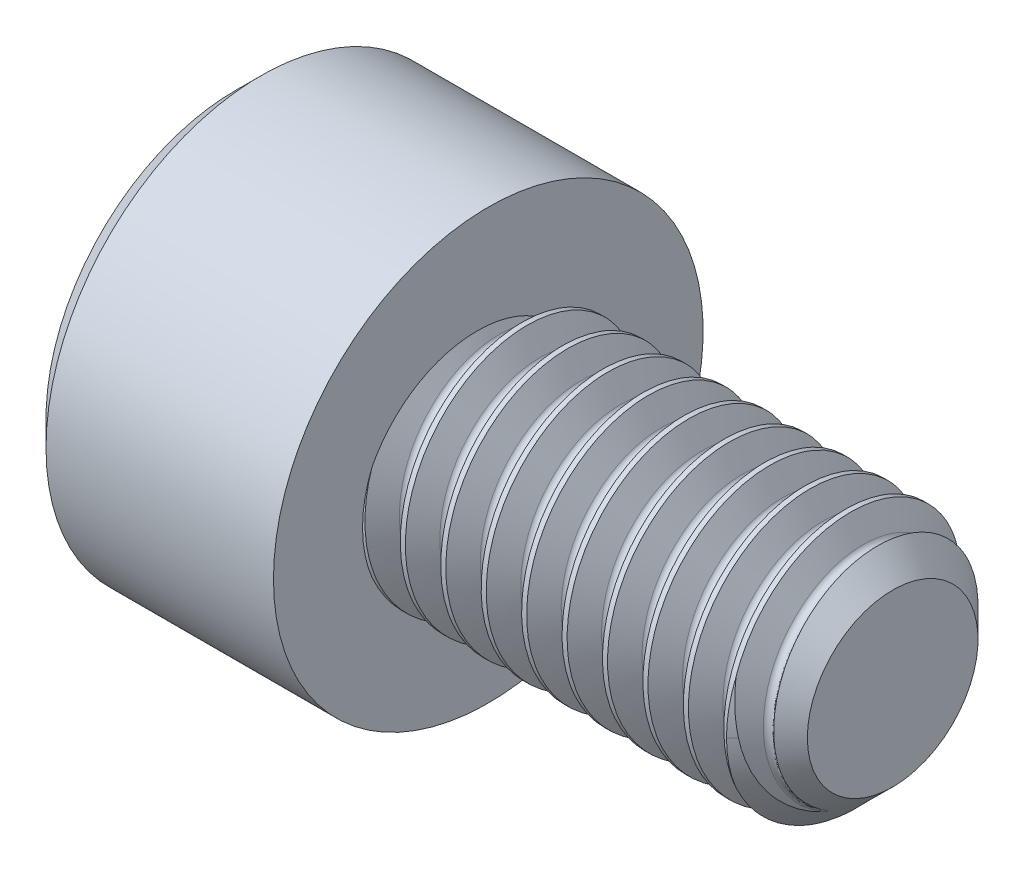
SolidWorks part; units mm, degrees
material "AISI Type 316L stainless steel"
ref_plane "Front Plane" through (0, 0, 0) normal (0, 0, 1) x (1, 0, 0)
ref_plane "Top Plane" through (0, 0, 0) normal (0, 1, 0) x (1, 0, 0)
ref_plane "Right Plane" through (0, 0, 0) normal (1, 0, 0) x (0, 0, -1)
sketch "Sketch1" plane through (0, 0, 0) normal (0, 0, 1) x (1, 0, 0)
  line L0 (-88.7055, 0) -> (96.9812, 0) construction
  line L1 (0, 0) -> (0, 4.25)
  line L2 (0, 4.25) -> (5, 4.25)
  line L4 (13, 0) -> (13, 2.488)
  line L5 (13, 2.488) -> (5, 2.488)
  line L6 (5, 2.488) -> (5, 4.25)
  line L7 (0, 0) -> (13, 0)
revolve "Revolve1" add sketch "Sketch1" angle 360 about L0
chamfer "Chamfer1" distance 0.8 angle 45 1 edges at (13, 0, 2.488)
chamfer "Chamfer2" distance 0.5 angle 45 1 edges at (0, 0, 4.25)
sketch "Sketch3" plane through (0, 0, 0) normal (1, 0, 0) x (0, 0, -1)
  line L1 (-2.3094, 0) -> (-1.1547, -2)
  line L2 (-1.1547, -2) -> (1.1547, -2)
  line L3 (1.1547, -2) -> (2.3094, 0)
  line L4 (2.3094, 0) -> (1.1547, 2)
  line L5 (1.1547, 2) -> (-1.1547, 2)
  line L6 (-1.1547, 2) -> (-2.3094, 0)
  circle A0 centre (0, 0) radius 2 construction
  dimension "D1" = 4
extrude "Cut-Extrude1" cut sketch "Sketch3" along normal blind 2.5
chamfer "Chamfer3" distance 0.4 angle 45 6 edges at (0, 2, 0) (0, 1, 1.7321) (0, -1, 1.7321) (0, -2, 0) (0, -1, -1.7321) (0, 1, -1.7321)
sketch "Sketch5" plane through (13, 0, 0) normal (1, 0, 0) x (0, 0, -1)
  circle A0 centre (0, 0) radius 2.488
curve "Helix/Spiral1" pitch 0.8 height 8 radius 2.488 centre (13, 0, 0) axis (-1, 0, 0) start towards (0, 0, -1)
sketch "Sketch8" plane through (0, 0, 0) normal (0, 1, 0) x (1, 0, 0)
  line L0 (13, 2.488) -> (13, 1.8816) construction
  line L1 (13.1, 2.0549) -> (13.5251, 2.7912)
  line L2 (13.5251, 2.7912) -> (12.4749, 2.7912)
  line L3 (12.4749, 2.7912) -> (12.9, 2.0549)
  line L4 (13, -1.688) -> (13, 1.688) construction
  circle A0 centre (13, 2.488) radius 0.3032 construction
  arc A1 (13.1, 2.0549) -> (12.9, 2.0549) centre (13, 2.1126) cw
  dimension "D2" = 0.1155
  dimension "D1" = 0.6064
sweep "Cut-Sweep1" cut profiles "Sketch8" path "Helix/Spiral1" align with end faces yes
